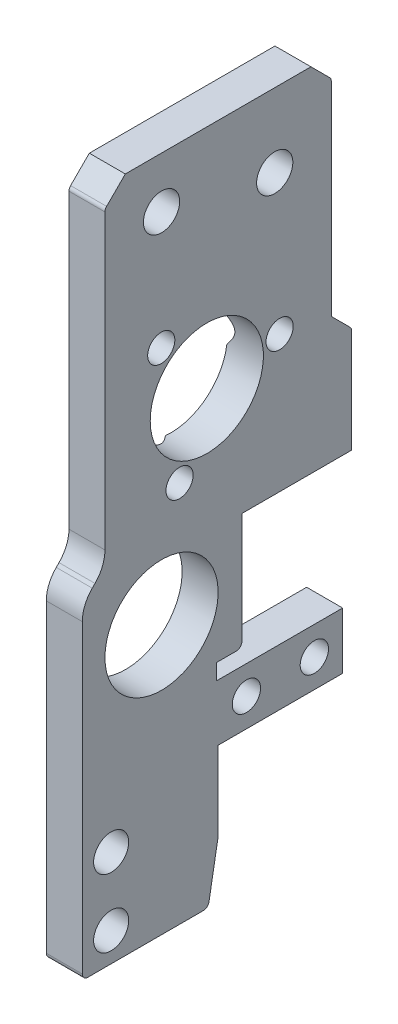
SolidWorks part; units mm, degrees
ref_plane "Front Plane" through (0, 0, 0) normal (0, 0, 1) x (1, 0, 0)
ref_plane "Top Plane" through (0, 0, 0) normal (0, 1, 0) x (1, 0, 0)
ref_plane "Right Plane" through (0, 0, 0) normal (1, 0, 0) x (0, 0, -1)
sketch "Sketch1" plane through (0, 0, 0) normal (1, 0, 0) x (0, 0, -1)
  line L2 (0, 0) -> (0, 28.7)
  line L3 (0, 28.7) -> (2, 30.7)
  line L4 (2, 30.7) -> (2, 59.81)
  line L5 (2, 59.81) -> (22, 59.81)
  line L7 (23.8, 28.68) -> (14.1, 28.68)
  line L8 (11.85, 18.4) -> (11.85, 17)
  line L9 (11.85, 17) -> (23, 17)
  line L10 (23, 17) -> (23, 12)
  line L11 (23, 12) -> (12, 12)
  line L12 (12, 12) -> (12, 0)
  line L13 (12, 0) -> (0, 0)
  line L14 (-8.9356, -4) -> (60.4069, -4) construction
  line L15 (7, 28.7) -> (0, 28.7) construction
  line L16 (2, 30.7) -> (2, 20.9492) construction
  line L18 (11.85, 18.4) -> (14.1, 18.4)
  line L19 (14.1, 18.4) -> (14.1, 28.68)
  line L23 (22, 59.81) -> (22, 39.81)
  line L26 (22, 39.81) -> (23.8, 39.81)
  line L27 (23.8, 39.81) -> (23.8, 28.68)
  circle A0 centre (7, 23.7) radius 5
  circle A1 centre (7, 55.31) radius 1.6
  circle A2 centre (17, 53.31) radius 1.6
  circle A3 centre (20.5, 14.5) radius 1.25
  circle A4 centre (14.5, 14.5) radius 1.25
  circle A5 centre (2.55, 2.55) radius 1.55
  circle A6 centre (2.55, 8.55) radius 1.55
  point P12 (6, 0)
  dimension "D11" = 10
  dimension "D13" = 3.2
  dimension "D17" = 5
  dimension "D21" = 2.5
  dimension "D29" = 6
  dimension "D28" = 3.1
  dimension "D30" = 2.55
  dimension "D2" = 59.81
  dimension "D3" = 31.13
  dimension "D4" = 5
  dimension "D5" = 11.68
  dimension "D6" = 11.15
  dimension "D7" = 10
  dimension "D8" = 4
  dimension "D9" = 2
  dimension "D10" = 2
  dimension "D12" = 36.11
  dimension "D14" = 6.5
  dimension "D15" = 4.5
  dimension "D16" = 5
  dimension "D18" = 6
  dimension "D19" = 2.5
  dimension "D20" = 2.5
  dimension "D22" = 1.4
  dimension "D23" = 2.25
  dimension "D24" = 20
  dimension "D25" = 11
  dimension "D26" = 1.8
  dimension "D27" = 20
  dimension "D31" = 2.55
extrude "Boss-Extrude1" add sketch "Sketch1" along normal blind 3.18
chamfer "Chamfer1" distance 5 angle 10 1 edges at (1.59, 0, -12) first distance on face at (1.59, 6, -12)
fillet "Fillet1" [suppressed] radius 1
sketch "Sketch3" plane through (0, 0, 0) normal (-1, 0, 0) x (0, 0, 1)
  line L1 (-17.4326, 40.7448) -> (-6.9749, 44.9147) construction
  line L2 (-6.9749, 44.9147) -> (-8.5925, 33.7732) construction
  line L3 (-8.5925, 33.7732) -> (-17.4326, 40.7448) construction
  line L4 (-2, 59.81) -> (-2, 30.7) construction
  circle A0 centre (-11, 39.8109) radius 5
  circle A2 centre (-11, 39.8109) radius 6.5 construction
  circle A3 centre (-6.9749, 44.9147) radius 1.2 construction
  circle A4 centre (-8.5925, 33.7732) radius 1.2 construction
  circle A5 centre (-17.4326, 40.7448) radius 1.2 construction
  circle A6 centre (-7, 23.7) radius 5 construction
  dimension "D1" = 10
  dimension "D3" = 16.6
  dimension "D4" = 13
  dimension "D5" = 2.4
  dimension "D2" = 9
hole_wizard "CSK for M2 Flat Head Machine Screw1" positions "Sketch6" profile "Sketch7" countersink size "M2" standard "ANSI Metric"
sketch "Sketch6" plane through (0, 0, 0) normal (-1, 0, 0) x (0, 0, 1)
  point P0 (-6.9749, 44.9147)
  point P3 (-17.4326, 40.7448)
  point P6 (-8.5925, 33.7732)
sketch "Sketch7" plane through (0, 44.9147, -6.9749) normal (0, 1, 0) x (0, 0, 1)
  line L0 (0, 0) -> (0, 4.23)
  line L1 (0, 4.23) -> (1.2, 3.509)
  line L2 (1.2, 3.509) -> (1.2, 1)
  line L3 (1.2, 1) -> (2.2, 0)
  line L5 (2.2, 0) -> (0, 0)
  line L6 (-1.2, 1) -> (-2.2, 0) construction
  line L10 (0, 4.23) -> (-1.2, 3.509) construction
  line L11 (0, -6.35) -> (0, 107.95) construction
  dimension "Hole Dia." = 2.4
  dimension "Hole Depth" = 4.23
  dimension "Near C'Sink Dia." = 4.4
  dimension "Near C'Sink Angle" = 90
  dimension "Drill Angle" = 118
extrude "Cut-Extrude4" cut sketch "Sketch3" against normal through all
sketch "Sketch8" plane through (3.18, 0, 0) normal (1, 0, 0) x (0, 0, -1)
  line L0 (2, 59.81) -> (2, 30.7) construction
  line L1 (11, 39.8109) -> (2, 39.8109) construction
  line L2 (2, 42.8109) -> (4.1261, 42.8109)
  line L3 (4.1261, 36.8109) -> (2, 36.8109)
  line L4 (2, 36.8109) -> (2, 42.8109)
  arc A0 (4.1261, 36.8109) -> (4.1261, 42.8109) centre (11, 39.8109) ccw
  circle A1 centre (7, 23.7) radius 5 construction
  point P11 (2, 39.8109)
  dimension "D1" = 16.6
  dimension "D2" = 15
  dimension "D3" = 9
  dimension "D4" = 6
extrude "Cut-Extrude5" [suppressed] cut sketch "Sketch8" against normal through all
fillet "Fillet2" radius 3 2 edges at (1.59, 28.7, 0) (1.59, 30.7, -2)
fillet "Chamfer2" radius 1.8 3 edges at (1.59, 59.81, -22) (1.59, 59.81, -2) (1.59, 39.81, -23.8) profile chamfer
fillet "Fillet4" radius 0.5 6 edges at (1.59, 58.01, -2) (1.59, 58.01, -22) (1.59, 18.4, -14.1) (1.59, 0, -11.1184) (1.59, 38.01, -23.8) (1.59, 0, 0)
